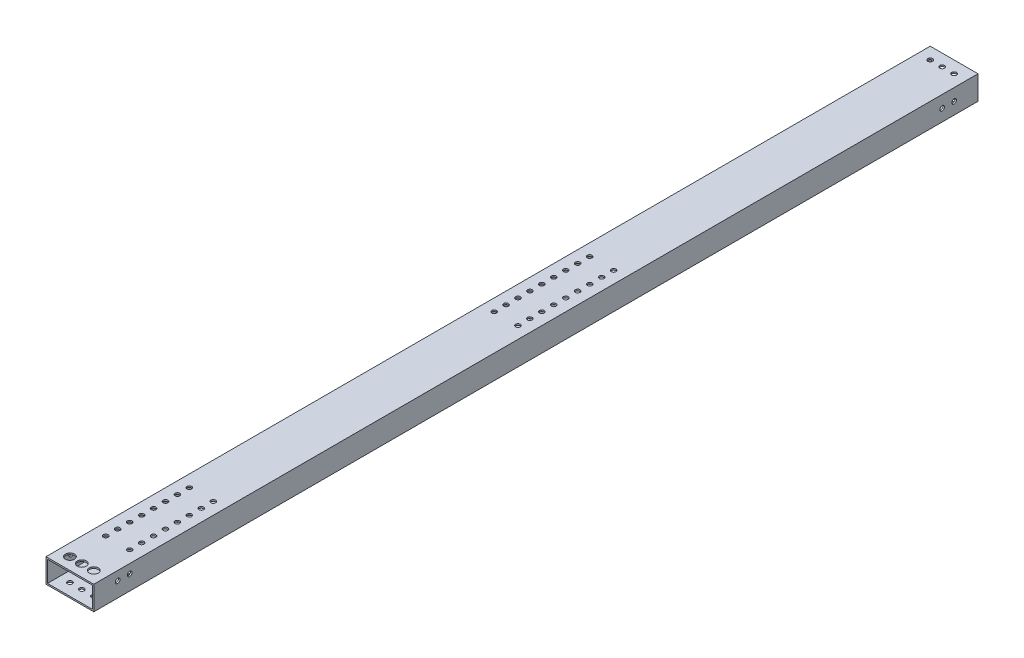
SolidWorks part; units mm, degrees
material "6061-T6 (SS)"
ref_plane "Front Plane" through (0, 0, 0) normal (0, 0, 1) x (1, 0, 0)
ref_plane "Top Plane" through (0, 0, 0) normal (0, 1, 0) x (1, 0, 0)
ref_plane "Right Plane" through (0, 0, 0) normal (1, 0, 0) x (0, 0, -1)
sketch "Sketch1" plane through (0, 0, 0) normal (0, 0, 1) x (1, 0, 0)
  line L0 (-23.8125, 11.1125) -> (23.8125, 11.1125)
  line L1 (-25.4, -12.7) -> (25.4, -12.7)
  line L2 (-25.4, -12.7) -> (-25.4, 12.7)
  line L3 (-25.4, 12.7) -> (25.4, 12.7)
  line L4 (25.4, -12.7) -> (25.4, 12.7)
  line L5 (-25.4, -12.7) -> (25.4, 12.7) construction
  line L6 (-25.4, 12.7) -> (25.4, -12.7) construction
  line L7 (23.8125, -11.1125) -> (23.8125, 11.1125)
  line L8 (-23.8125, -11.1125) -> (23.8125, -11.1125)
  line L9 (-23.8125, -11.1125) -> (-23.8125, 11.1125)
  point P0 (0, 0)
  dimension "D1" = 50.8
  dimension "D2" = 25.4
  dimension "D3" = 1.5875
extrude "Boss-Extrude1" add sketch "Sketch1" along normal mid plane 939.8
sketch "Sketch4" plane through (0, 12.7, 0) normal (0, 1, 0) x (1, 0, 0)
  line L0 (25.4, -469.9) -> (-25.4, -469.9) construction
  circle A0 centre (-12.7, -457.2) radius 4.826
  circle A1 centre (0, -457.2) radius 4.826
  circle A2 centre (12.7, -457.2) radius 4.826
  dimension "D1" = 9.652
  dimension "D2" = 12.7
  dimension "D3" = 12.7
  dimension "D4" = 12.7
extrude "Cut-Extrude3" cut sketch "Sketch4" against normal up to surface (1.5875 mm away) contours A0 | A1 | A2 region at (-12.7, 12.7, 457.2) region at (0, 12.7, 457.2) region at (12.7, 12.7, 457.2) up to face at (0, 11.1125, 0)
sketch "Sketch5" plane through (0, -12.7, 0) normal (0, -1, 0) x (1, 0, 0)
  circle A0 centre (-12.7, 457.2) radius 4.826 construction
  circle A1 centre (0, 457.2) radius 4.826 construction
  circle A2 centre (12.7, 457.2) radius 4.826 construction
  circle A3 centre (-12.7, 457.2) radius 4.826
  circle A4 centre (0, 457.2) radius 4.826
  circle A5 centre (12.7, 457.2) radius 4.826
  circle A6 centre (-12.7, 457.2) radius 2.5527
  circle A7 centre (0, 457.2) radius 2.5527
  circle A8 centre (12.7, 457.2) radius 2.5527
  dimension "D1" = 5.1054
extrude "Cut-Extrude4" cut sketch "Sketch5" against normal up to surface (1.5875 mm away) contours A8 | A7 | A6 region at (-12.7, -12.7, 457.2) region at (0, -12.7, 457.2) region at (12.7, -12.7, 457.2) up to face at (0, -11.1125, 0)
sketch "Sketch6" plane through (0, -12.7, 0) normal (0, -1, 0) x (1, 0, 0)
  line L0 (-25.4, -469.9) -> (25.4, -469.9) construction
  circle A0 centre (-12.7, -457.2) radius 2.5527
  circle A1 centre (0, -457.2) radius 2.5527
  circle A2 centre (12.7, -457.2) radius 2.5527
  dimension "D1" = 5.1054
  dimension "D2" = 12.7
  dimension "D3" = 12.7
  dimension "D4" = 12.7
extrude "Cut-Extrude5" cut sketch "Sketch6" against normal through all contours A2 | A1 | A0 region at (-12.7, -12.7, -457.2) region at (0, -12.7, -457.2) region at (12.7, -12.7, -457.2)
sketch "Sketch7" plane through (25.4, 0, 0) normal (1, 0, 0) x (0, 0, -1)
  line L0 (-469.9, -12.7) -> (-469.9, 12.7) construction
  line L2 (469.9, -12.7) -> (469.9, 12.7) construction
  line L3 (-469.9, -12.7) -> (469.9, -12.7) construction
  circle A0 centre (-457.2, 3.175) radius 2.4892
  circle A1 centre (-444.5, 3.175) radius 2.4892
  circle A2 centre (-431.8, 3.175) radius 2.4892
  circle A3 centre (-419.1, 3.175) radius 2.4892
  circle A4 centre (457.2, 0) radius 2.4892
  circle A5 centre (444.5, 0) radius 2.4892
  circle A6 centre (431.8, 0) radius 2.4892
  dimension "D1" = 4.9784
  dimension "D7" = 4.9784
  dimension "D8" = 12.7
  dimension "D2" = 12.7
  dimension "D3" = 12.7
  dimension "D4" = 12.7
  dimension "D5" = 12.7
  dimension "D6" = 15.875
  dimension "D9" = 12.7
  dimension "D10" = 12.7
  dimension "D11" = 12.7
extrude "Cut-Extrude6" cut sketch "Sketch7" against normal through all contours A6 | A5 | A1 | A2 region at (25.4, 3.175, 444.5) region at (25.4, 3.175, 431.8) region at (25.4, 0, -444.5) region at (25.4, 0, -431.8)
sketch "Sketch10" plane through (0, 12.7, 0) normal (0, 1, 0) x (1, 0, 0)
  line L1 (25.4, -469.9) -> (-25.4, -469.9) construction
  line L3 (-25.4, -469.9) -> (-25.4, 469.9) construction
  circle A0 centre (-12.7, -419.1) radius 2.4892
  circle A5 centre (12.7, -419.1) radius 2.4892
  circle A6 centre (-12.7, -406.4) radius 2.4892
  circle A7 centre (12.7, -406.4) radius 2.4892
  circle A8 centre (-12.7, -393.7) radius 2.4892
  circle A9 centre (12.7, -393.7) radius 2.4892
  circle A10 centre (-12.7, -381) radius 2.4892
  circle A11 centre (12.7, -381) radius 2.4892
  circle A12 centre (-12.7, -368.3) radius 2.4892
  circle A13 centre (12.7, -368.3) radius 2.4892
  circle A14 centre (-12.7, -355.6) radius 2.4892
  circle A15 centre (12.7, -355.6) radius 2.4892
  circle A16 centre (-12.7, -342.9) radius 2.4892
  circle A17 centre (12.7, -342.9) radius 2.4892
  circle A18 centre (-12.7, -330.2) radius 2.4892
  circle A19 centre (12.7, -330.2) radius 2.4892
  circle A20 centre (-12.7, -6.35) radius 2.4892
  circle A21 centre (12.7, -6.35) radius 2.4892
  circle A22 centre (-12.7, 6.35) radius 2.4892
  circle A23 centre (12.7, 6.35) radius 2.4892
  circle A24 centre (-12.7, 19.05) radius 2.4892
  circle A25 centre (12.7, 19.05) radius 2.4892
  circle A26 centre (-12.7, 31.75) radius 2.4892
  circle A27 centre (12.7, 31.75) radius 2.4892
  circle A28 centre (-12.7, 44.45) radius 2.4892
  circle A29 centre (12.7, 44.45) radius 2.4892
  circle A30 centre (-12.7, 57.15) radius 2.4892
  circle A31 centre (12.7, 57.15) radius 2.4892
  circle A32 centre (-12.7, 69.85) radius 2.4892
  circle A33 centre (12.7, 69.85) radius 2.4892
  circle A34 centre (-12.7, 82.55) radius 2.4892
  circle A35 centre (12.7, 82.55) radius 2.4892
  circle A36 centre (-12.7, 95.25) radius 2.4892
  circle A37 centre (12.7, 95.25) radius 2.4892
  point P60 (0, 0)
  dimension "D1" = 25.4
  dimension "D3" = 4.9784
  dimension "D2" = 12.7
  dimension "D4" = 50.8
  dimension "D5" = 12.7
  dimension "D6" = 323.85
  dimension "D8" = 12.7
  dimension "D9" = 9
extrude "Cut-Extrude8" cut sketch "Sketch10" against normal through all
